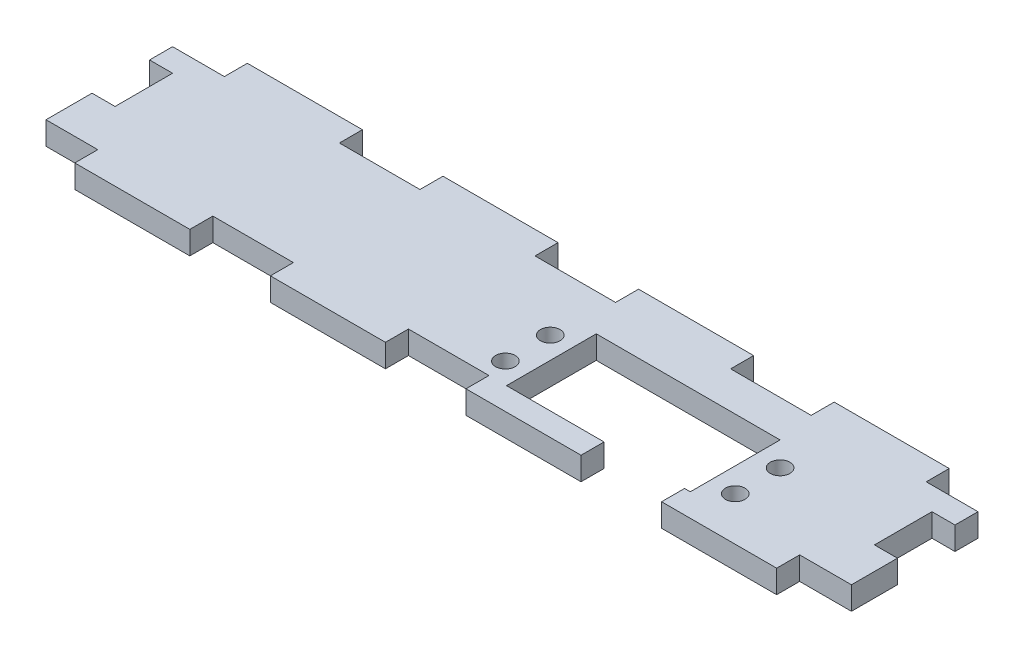
SolidWorks part; units mm, degrees
ref_plane "Front Plane" through (0, 0, 0) normal (0, 0, 1) x (1, 0, 0)
ref_plane "Top Plane" through (0, 0, 0) normal (0, 1, 0) x (1, 0, 0)
ref_plane "Right Plane" through (0, 0, 0) normal (1, 0, 0) x (0, 0, -1)
sketch "Sketch1" plane through (0, 0, 0) normal (0, 1, 0) x (1, 0, 0)
  line L1 (0, 0) -> (-177.8, 0)
  line L2 (0, 0) -> (0, -38.1)
  line L3 (0, -38.1) -> (-177.8, -38.1)
  line L4 (-177.8, 0) -> (-177.8, -38.1)
  dimension "D1" = 177.8
  dimension "D2" = 38.1
extrude "Boss-Extrude1" add sketch "Sketch1" along normal blind 5.08
sketch "Sketch2" plane through (0, 5.08, 0) normal (0, 1, 0) x (1, 0, 0)
  line L0 (-177.8, 0) -> (-177.8, -38.1) construction
  line L1 (-177.8, -33.02) -> (-166.37, -33.02)
  line L2 (-177.8, -33.02) -> (-177.8, -38.1)
  line L3 (-177.8, -38.1) -> (-166.37, -38.1)
  line L4 (-166.37, -33.02) -> (-166.37, -38.1)
  line L5 (-177.8, -38.1) -> (0, -38.1) construction
  dimension "D1" = 5.08
  dimension "D2" = 11.43
extrude "Cut-Extrude1" cut sketch "Sketch2" against normal up to surface (5.08 mm away) up to face at (-88.9, 0, 19.05)
sketch "Sketch3" plane through (0, 5.08, 0) normal (0, 1, 0) x (1, 0, 0)
  line L0 (-166.37, -38.1) -> (0, -38.1) construction
  line L1 (-11.43, -33.02) -> (0, -33.02)
  line L2 (-11.43, -33.02) -> (-11.43, -38.1)
  line L3 (-11.43, -38.1) -> (0, -38.1)
  line L4 (0, -33.02) -> (0, -38.1)
  line L5 (0, -38.1) -> (0, 0) construction
  dimension "D1" = 11.43
  dimension "D2" = 5.08
extrude "Cut-Extrude2" cut sketch "Sketch3" against normal up to surface (5.08 mm away) up to face at (-114.7233, 0, 23.7067)
sketch "Sketch4" plane through (0, 5.08, 0) normal (0, 1, 0) x (1, 0, 0)
  line L0 (-166.37, -38.1) -> (-11.43, -38.1) construction
  line L1 (-140.97, -33.02) -> (-123.19, -33.02)
  line L2 (-140.97, -33.02) -> (-140.97, -38.1)
  line L3 (-140.97, -38.1) -> (-123.19, -38.1)
  line L4 (-123.19, -33.02) -> (-123.19, -38.1)
  line L5 (-166.37, -38.1) -> (-166.37, -33.02) construction
  dimension "D1" = 5.08
  dimension "D2" = 17.78
  dimension "D3" = 25.4
extrude "Cut-Extrude3" cut sketch "Sketch4" against normal up to surface (5.08 mm away) up to face at (-88.9, 0, 26.035)
pattern_linear "LPattern1" count 3 spacing 43.18 along (1, 0, 0) of "Cut-Extrude3"
sketch "Sketch5" plane through (0, 5.08, 0) normal (0, 1, 0) x (1, 0, 0)
  line L1 (-76.1365, -13.208) -> (-35.56, -13.208)
  line L2 (-76.1365, -13.208) -> (-76.1365, -33.02)
  line L3 (-76.1365, -33.02) -> (-35.56, -33.02)
  line L4 (-35.56, -13.208) -> (-35.56, -33.02)
  line L5 (0, -33.02) -> (0, 0) construction
  line L6 (-36.83, -38.1) -> (-11.43, -38.1) construction
  dimension "D1" = 40.5765
  dimension "D2" = 19.812
  dimension "D3" = 5.08
  dimension "D4" = 35.56
extrude "Cut-Extrude4" cut sketch "Sketch5" against normal up to surface (5.08 mm away) up to face at (-88.9, 0, 31.75)
sketch "Sketch6" plane through (0, 0, 0) normal (0, -1, 0) x (-1, 0, 0)
  line L1 (0, -10.16) -> (5.08, -10.16)
  line L2 (0, -10.16) -> (0, -22.86)
  line L3 (0, -22.86) -> (5.08, -22.86)
  line L4 (5.08, -10.16) -> (5.08, -22.86)
  line L6 (0, -33.02) -> (0, 0) construction
  line L7 (0, 0) -> (177.8, 0) construction
  line L8 (0, -33.02) -> (11.43, -33.02) construction
  dimension "D1" = 5.08
  dimension "D2" = 12.7
  dimension "D3" = 10.16
  dimension "D4" = 10.16
extrude "Cut-Extrude5" cut sketch "Sketch6" against normal up to surface (5.08 mm away) up to face at (-83.3914, 5.08, 30.3107)
sketch "Sketch7" plane through (0, 5.08, 0) normal (0, 1, 0) x (1, 0, 0)
  line L0 (0, 0) -> (-177.8, 0) construction
  line L1 (-177.8, 0) -> (-166.37, 0)
  line L2 (-177.8, 0) -> (-177.8, -5.08)
  line L3 (-177.8, -5.08) -> (-166.37, -5.08)
  line L4 (-166.37, 0) -> (-166.37, -5.08)
  line L5 (-177.8, 0) -> (-177.8, -33.02) construction
  line L6 (-166.37, -38.1) -> (-166.37, -33.02) construction
  line L7 (-140.97, -33.02) -> (-140.97, -38.1) construction
  line L8 (-140.97, 0) -> (-123.19, 0)
  line L9 (-140.97, 0) -> (-140.97, -5.08)
  line L10 (-140.97, -5.08) -> (-123.19, -5.08)
  line L11 (-123.19, 0) -> (-123.19, -5.08)
  line L12 (-123.19, -38.1) -> (-123.19, -33.02) construction
  line L13 (0, -10.16) -> (0, 0) construction
  line L14 (-11.43, 0) -> (0, 0)
  line L15 (-11.43, 0) -> (-11.43, -5.08)
  line L16 (-11.43, -5.08) -> (0, -5.08)
  line L17 (0, 0) -> (0, -5.08)
  line L18 (-11.43, -33.02) -> (-11.43, -38.1) construction
  dimension "D1" = 5.08
  dimension "D2" = 0
  dimension "D3" = 5.08
  dimension "D4" = 0
  dimension "D5" = 0
  dimension "D6" = 5.08
  dimension "D7" = 0
extrude "Cut-Extrude6" cut sketch "Sketch7" against normal up to surface (5.08 mm away) up to face at (-71.8412, 0, 28.3391)
sketch "Sketch8" plane through (0, 5.08, 0) normal (0, 1, 0) x (1, 0, 0)
  line L0 (-11.43, 0) -> (-123.19, 0) construction
  line L1 (-97.79, 0) -> (-80.01, 0)
  line L2 (-97.79, 0) -> (-97.79, -5.08)
  line L3 (-97.79, -5.08) -> (-80.01, -5.08)
  line L4 (-80.01, 0) -> (-80.01, -5.08)
  line L5 (-97.79, -33.02) -> (-97.79, -38.1) construction
  line L6 (-80.01, -38.1) -> (-80.01, -33.02) construction
  dimension "D1" = 5.08
  dimension "D2" = 0
  dimension "D3" = 0
extrude "Cut-Extrude7" cut sketch "Sketch8" against normal up to surface (5.08 mm away) up to face at (-80.4298, 0, 22.8882)
pattern_linear "LPattern2" count 2 spacing 43.18 along (1, 0, 0) of "Cut-Extrude7"
sketch "Sketch9" plane through (0, 5.08, 0) normal (0, 1, 0) x (1, 0, 0)
  line L0 (-177.8, -5.08) -> (-177.8, -33.02) construction
  line L1 (-177.8, -10.16) -> (-172.72, -10.16)
  line L2 (-177.8, -10.16) -> (-177.8, -22.86)
  line L3 (-177.8, -22.86) -> (-172.72, -22.86)
  line L4 (-172.72, -10.16) -> (-172.72, -22.86)
  line L5 (0, -10.16) -> (-5.08, -10.16) construction
  line L6 (-5.08, -22.86) -> (0, -22.86) construction
  dimension "D1" = 0
  dimension "D2" = 0
  dimension "D3" = 5.08
extrude "Cut-Extrude8" cut sketch "Sketch9" against normal up to surface (5.08 mm away) up to face at (-78.0444, 0, 19.1885)
sketch "Sketch10" plane through (0, 0, 0) normal (0, -1, 0) x (1, 0, 0)
  line L0 (-76.1365, 13.208) -> (-76.1365, 33.02) construction
  line L1 (-35.56, 13.208) -> (-76.1365, 13.208) construction
  line L5 (-35.56, 33.02) -> (-35.56, 13.208) construction
  circle A0 centre (-80.9625, 18.542) radius 2.159
  circle A1 centre (-80.9625, 28.448) radius 2.159
  circle A2 centre (-30.226, 28.448) radius 2.159
  circle A3 centre (-30.226, 18.542) radius 2.159
  dimension "D1" = 4.318
  dimension "D5" = 4.318
  dimension "D6" = 5.334
  dimension "D2" = 9.906
  dimension "D3" = 4.826
  dimension "D4" = 5.334
  dimension "D7" = 9.906
  dimension "D8" = 5.334
extrude "Cut-Extrude9" cut sketch "Sketch10" against normal up to surface (5.08 mm away) up to face at (-86.1457, 5.08, 18.9653)
